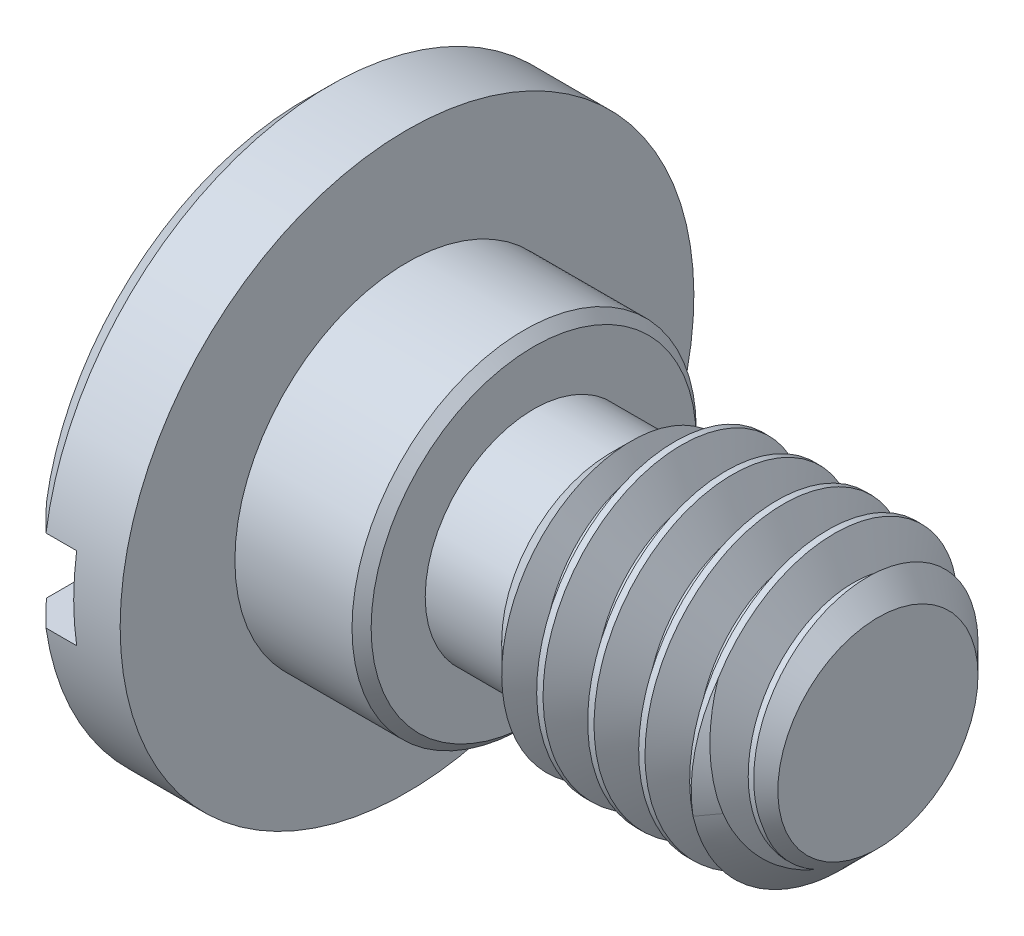
SolidWorks part; units mm, degrees
ref_plane "Front Plane" through (0, 0, 0) normal (0, 0, 1) x (1, 0, 0)
ref_plane "Top Plane" through (0, 0, 0) normal (0, 1, 0) x (1, 0, 0)
ref_plane "Right Plane" through (0, 0, 0) normal (1, 0, 0) x (0, 0, -1)
sketch "Sketch1" plane through (0, 0, 0) normal (0, 0, 1) x (1, 0, 0)
  line L0 (-7.9375, 0) -> (7.9375, 0) construction
  line L1 (-7.9375, 7.9375) -> (-7.9375, -7.9375) construction
  line L2 (-1.5875, 4.7625) -> (-1.5875, -4.7625) construction
  line L3 (7.9375, 3.9688) -> (7.9375, -3.9688) construction
  line L4 (-5.0927, 7.9375) -> (-5.0927, -7.9375) construction
  line L5 (7.9375, -3.9688) -> (7.9375, -4.7625) construction
  point P2 (2.9986, -3.9688)
  point P8 (-1.5875, 0)
  dimension "B" = 15.875
  dimension "E" = 9.525
  dimension "thread size" = 7.9375
  dimension "C" = 6.35
  dimension "D" = 3.5052
  dimension "A" = 15.875
  dimension "D1" = 9.525
  dimension "D2" = 2.8448
  dimension "D3" = 0.7938
  dimension "D4" = 4.9389
ref_plane "Plane1" through (7.9375, 0, 0) normal (1, 0, 0) x (0, 0, -1)
sketch "Sketch2" plane through (7.9375, 0, 0) normal (1, 0, 0) x (0, 0, -1)
  circle A0 centre (0, 0) radius 3.9688
extrude "Extrude1" add sketch "Sketch2" against normal up to vertex (9.525 mm away) up to point (-1.5875, 4.7625, 0)
sketch "Sketch3" plane through (7.9375, 0, 0) normal (1, 0, 0) x (0, 0, -1)
  circle A1 centre (0, 0) radius 3.9688
  circle A2 centre (0, 0) radius 3.9688
  dimension "D1" = 0
curve "Helix/Spiral1" pitch 1.4111 height 10.3187 turns 7.3125 parameters "pitch"=1.4111
chamfer "Chamfer1" distance 1.1994 angle 45 1 edges at (7.9375, 0, -3.9688)
sketch "Sketch4" plane through (0, 0, 0) normal (0, 0, 1) x (1, 0, 0)
  line L0 (9.1722, 3.9688) -> (7.9375, 3.9688)
  line L1 (7.9375, 3.9688) -> (8.4667, 3.0522)
  line L2 (8.4667, 3.0522) -> (8.6431, 3.0522)
  line L3 (8.6431, 3.0522) -> (9.1722, 3.9688)
  line L4 (8.5549, 3.0522) -> (8.5549, 3.9688) construction
  line L5 (8.9076, 3.5105) -> (8.2021, 3.5105) construction
  dimension "D1" = 60
  dimension "D2" = 0.1764
  dimension "D3" = 0.7056
sweep "Cut-Sweep1" cut profiles "Sketch4" path "Helix/Spiral1" align with end faces yes
sketch "Sketch5" plane through (0, 0, 0) normal (0, 0, 1) x (1, 0, 0)
  line L0 (-1.5875, 3.9687) -> (-1.5875, 3.0014)
  line L1 (-1.5875, 3.0014) -> (0.5292, 3.0014)
  line L2 (0.5292, 3.0014) -> (1.4965, 3.9687)
  line L3 (1.4965, 3.9687) -> (-1.5875, 3.9687)
  line L4 (-1.5875, 4.7625) -> (-1.5875, -4.7625) construction
  dimension "D1" = 2.1167
  dimension "D2" = 45
revolve "Cut-Revolve1" cut sketch "Sketch5" angle 360 about L0
sketch "Sketch6" plane through (-1.5875, 0, 0) normal (-1, 0, 0) x (0, 0, 1)
  circle A0 centre (0, 0) radius 4.7625
extrude "Extrude2" add sketch "Sketch6" along normal up to vertex (3.5052 mm away) up to point (-5.0927, 7.9375, 0)
sketch "Sketch7" plane through (-5.0927, 0, 0) normal (-1, 0, 0) x (0, 0, 1)
  circle A0 centre (0, 0) radius 7.9375
extrude "Extrude3" add sketch "Sketch7" along normal up to vertex (2.8448 mm away) up to point (-7.9375, 7.9375, 0)
chamfer "Chamfer2" distance 0.2646 angle 45 1 edges at (-1.5875, 0, 4.7625)
chamfer "Chamfer3" distance 0.7112 angle 45 1 edges at (-7.9375, 0, 7.9375)
sketch "Sketch8" plane through (-7.9375, 0, 0) normal (-1, 0, 0) x (0, 0, 1)
  line L0 (-7.9375, 0) -> (7.9375, 0)
  line L1 (0, 7.9375) -> (0, -7.9375) construction
extrude "Cut-Extrude-Thin1" cut sketch "Sketch8" against normal blind 1.5593 thin thin type mid plane wall 2.2758
sketch "Sketch9" [suppressed] plane through (-5.5562, 0, 0) normal (-1, 0, 0) x (0, 0, 1)
  line L1 (0, 1.5071) -> (-1.3052, 0.7536)
  line L2 (-1.3052, 0.7536) -> (-1.3052, -0.7536)
  line L3 (-1.3052, -0.7536) -> (0, -1.5071)
  line L4 (0, -1.5071) -> (1.3052, -0.7536)
  line L5 (1.3052, -0.7536) -> (1.3052, 0.7536)
  line L6 (1.3052, 0.7536) -> (0, 1.5071)
  circle A0 centre (0, 0) radius 1.3052 construction
  dimension "Hex" = 2.6104
extrude "Extrude4" [suppressed] cut sketch "Sketch9" against normal up to surface (2.2225 mm away)
sketch "Sketch10" [suppressed] plane through (-5.5562, 0, 0) normal (-1, 0, 0) x (0, 0, 1)
  circle A0 centre (0, 0) radius 1.5071
extrude "Extrude5" [suppressed] cut sketch "Sketch10" against normal through all draft 45
equation "\"D2@Sketch4\" = \"pitch@Helix/Spiral1\"*.125"
equation "\"D3@Sketch4\" = \"pitch@Helix/Spiral1\"*.5"
equation "\"D1@Chamfer1\" = \"pitch@Helix/Spiral1\"*.850"
equation "\"D3@Helix/Spiral1\" = \"D1@Sketch1\"+.03125"
equation "\"D1@Sketch5\" = \"pitch@Helix/Spiral1\"*1.5"
equation "\"D1@Chamfer3\" = \"D2@Sketch1\"/4"
equation "\"D1@Cut-Extrude-Thin1\" = \"D1@Chamfer1\"*1.3"
equation "\"D1@Chamfer2\" = \"D3@Sketch1\"/3"
equation "\"D5@Cut-Extrude-Thin1\" = \"D2@Sketch1\"*.8"
equation "\"D4@Sketch1\" = \"pitch@Helix/Spiral1\"*3.50"
